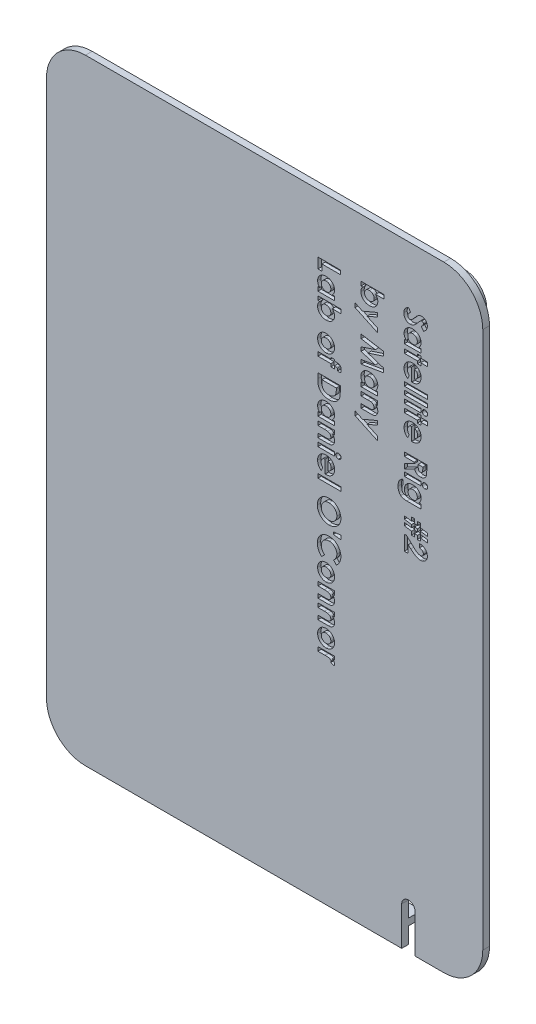
SolidWorks part; units mm, degrees
ref_plane "Front Plane" through (0, 0, 0) normal (0, 0, 1) x (1, 0, 0)
ref_plane "Top Plane" through (0, 0, 0) normal (0, 1, 0) x (1, 0, 0)
ref_plane "Right Plane" through (0, 0, 0) normal (1, 0, 0) x (0, 0, -1)
sketch "Sketch1" plane through (0, 0, 0) normal (0, 0, 1) x (1, 0, 0)
  line L0 (40, 65.2) -> (-40, 65.2) construction
  line L1 (45.2, -60) -> (45.2, 60) construction
  line L2 (-40, -65.2) -> (40, -65.2) construction
  line L3 (-45.2, 60) -> (-45.2, -60) construction
  line L4 (40, 65.2) -> (-40, 65.2) construction
  line L5 (45.2, -60) -> (45.2, 60) construction
  line L6 (-40, -65.2) -> (40, -65.2) construction
  line L7 (-45.2, 60) -> (-45.2, -60) construction
  line L8 (40, 65.1) -> (-40, 65.1)
  line L9 (-45.1, 60) -> (-45.1, -60)
  line L10 (-40, -65.1) -> (40, -65.1)
  line L11 (45.1, -60) -> (45.1, 60)
  line L12 (40, 63.6) -> (-40, 63.6)
  line L13 (-43.6, 60) -> (-43.6, -60)
  line L14 (-40, -63.6) -> (40, -63.6)
  line L15 (43.6, -60) -> (43.6, 60)
  arc A0 (-40, 65.2) -> (-45.2, 60) centre (-40, 60) ccw construction
  arc A1 (45.2, 60) -> (40, 65.2) centre (40, 60) ccw construction
  arc A2 (-45.2, -60) -> (-40, -65.2) centre (-40, -60) ccw construction
  arc A3 (40, -65.2) -> (45.2, -60) centre (40, -60) ccw construction
  arc A4 (-40, 65.2) -> (-45.2, 60) centre (-40, 60) ccw construction
  arc A5 (45.2, 60) -> (40, 65.2) centre (40, 60) ccw construction
  arc A6 (-45.2, -60) -> (-40, -65.2) centre (-40, -60) ccw construction
  arc A7 (40, -65.2) -> (45.2, -60) centre (40, -60) ccw construction
  arc A8 (-40, 65.1) -> (-45.1, 60) centre (-40, 60) ccw
  arc A9 (-45.1, -60) -> (-40, -65.1) centre (-40, -60) ccw
  arc A10 (40, -65.1) -> (45.1, -60) centre (40, -60) ccw
  arc A11 (45.1, 60) -> (40, 65.1) centre (40, 60) ccw
  arc A12 (-40, 63.6) -> (-43.6, 60) centre (-40, 60) ccw
  arc A13 (-43.6, -60) -> (-40, -63.6) centre (-40, -60) ccw
  arc A14 (40, -63.6) -> (43.6, -60) centre (40, -60) ccw
  arc A15 (43.6, 60) -> (40, 63.6) centre (40, 60) ccw
  dimension "D1" = 0.1
  dimension "D2" = 1.5
extrude "Boss-Extrude1" add sketch "Sketch1" against normal blind 3
sketch "Sketch3" plane through (0, 0, 0) normal (0, 0, 1) x (1, 0, 0)
  line L0 (40, 68.7) -> (-40, 68.7) construction
  line L1 (-48.7, 60) -> (-48.7, -60) construction
  line L2 (48.7, -60) -> (48.7, 60) construction
  line L3 (-40, -68.7) -> (40, -68.7) construction
  line L4 (40, 68.7) -> (-40, 68.7)
  line L5 (-48.7, 60) -> (-48.7, -60)
  line L6 (48.7, -60) -> (48.7, 60)
  line L7 (-40, -68.7) -> (40, -68.7)
  arc A0 (-40, 68.7) -> (-48.7, 60) centre (-40, 60) ccw construction
  arc A1 (48.7, 60) -> (40, 68.7) centre (40, 60) ccw construction
  arc A2 (40, -68.7) -> (48.7, -60) centre (40, -60) ccw construction
  arc A3 (-48.7, -60) -> (-40, -68.7) centre (-40, -60) ccw construction
  arc A4 (-40, 68.7) -> (-48.7, 60) centre (-40, 60) ccw
  arc A5 (48.7, 60) -> (40, 68.7) centre (40, 60) ccw
  arc A6 (40, -68.7) -> (48.7, -60) centre (40, -60) ccw
  arc A7 (-48.7, -60) -> (-40, -68.7) centre (-40, -60) ccw
extrude "Boss-Extrude2" add sketch "Sketch3" along normal blind 1.5
sketch "Sketch6" plane through (0, 0, -3) normal (0, 0, -1) x (-1, 0, 0)
  line L1 (40, -68.7) -> (-40, -68.7) construction
  line L2 (-33.6, -68.7) -> (-30.6, -68.7)
  line L3 (-33.6, -68.7) -> (-33.6, -58.6)
  line L4 (-33.6, -58.6) -> (-30.6, -58.6)
  line L7 (-30.6, -68.7) -> (-30.6, -58.6)
  line L8 (40, -63.6) -> (-40, -63.6) construction
  line L9 (-43.6, -60) -> (-43.6, 60) construction
  dimension "D1" = 3
  dimension "D2" = 5
  dimension "D3" = 10
extrude "Cut-Extrude2" cut sketch "Sketch6" against normal through all
fillet "Fillet1" radius 1.5 2 edges at (33.6, -58.6, 0.75) (30.6, -58.6, 0.75)
sketch "Sketch8" plane through (0, 0, 1.5) normal (0, 0, 1) x (1, 0, 0)
  line L0 (31.2, 56.2) -> (31.2, -23.6219) construction
  line L1 (40, 68.7) -> (-40, 68.7) construction
  line L2 (48.7, -60) -> (48.7, 60) construction
  text T0 "<b>Satellite Rig #2</b>\r\n<b>by Many</b>\r\n<b>Lab of Daniel O'Connor</b>" font "Century Gothic" height 5
  dimension "D1" = 12.5
  dimension "D2" = 17.5
extrude "Cut-Extrude4" cut sketch "Sketch8" against normal blind 0.75
